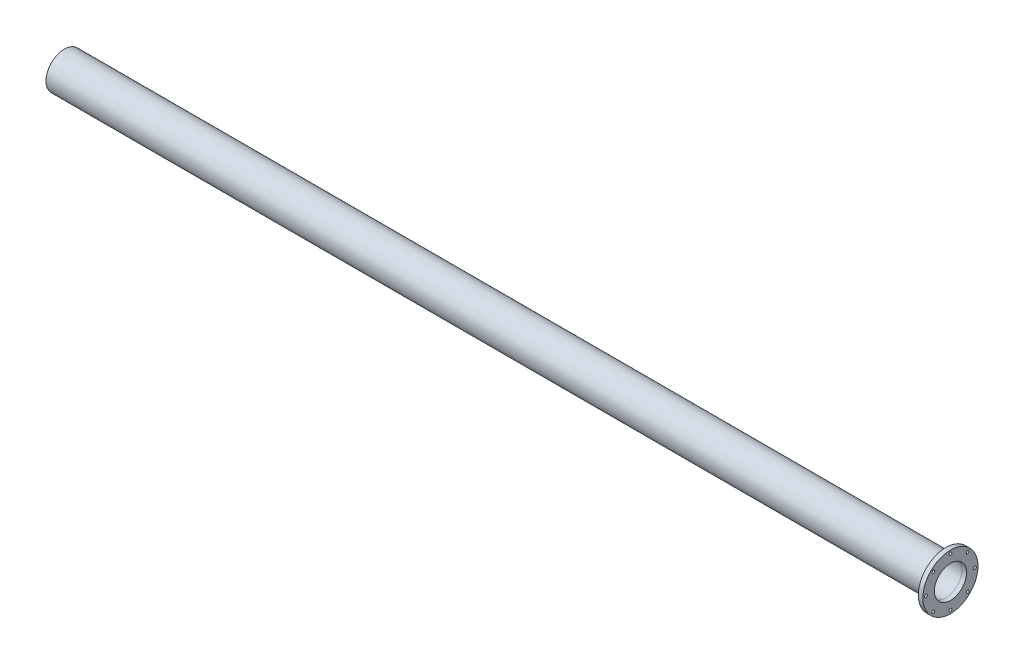
SolidWorks part; units mm, degrees
material "Galvanized Steel"
ref_plane "Front Plane" through (0, 0, 0) normal (0, 0, 1) x (1, 0, 0)
ref_plane "Top Plane" through (0, 0, 0) normal (0, 1, 0) x (1, 0, 0)
ref_plane "Right Plane" through (0, 0, 0) normal (1, 0, 0) x (0, 0, -1)
sketch "Sketch1" plane through (0, 0, 0) normal (1, 0, 0) x (0, 0, -1)
  circle A0 centre (0, 0) radius 44.45
  circle A1 centre (0, 0) radius 50.8
  dimension "D1" = 88.9
  dimension "D2" = 101.6
extrude "Boss-Extrude1" add sketch "Sketch1" along normal blind 1219.2 and the other way blind 1219.2
sketch "Sketch2" plane through (1219.2, 0, 0) normal (1, 0, 0) x (0, 0, -1)
  circle A0 centre (0, 0) radius 76.2
  circle A2 centre (0, 0) radius 44.45
  dimension "D1" = 152.4
extrude "Boss-Extrude2" add sketch "Sketch2" along normal blind 12.7 separate body
sketch "Sketch3" plane through (1231.9, 0, 0) normal (1, 0, 0) x (0, 0, -1)
  circle A0 centre (67.4688, 0) radius 3.9687
  dimension "D1" = 7.9375
  dimension "D2" = 67.4688
extrude "Cut-Extrude1" cut sketch "Sketch3" against normal blind 12.7
pattern_circular "CirPattern1" count 8 every 45 about axis through (1231.9, 0, 0) along (1, 0, 0) of "Cut-Extrude1"
